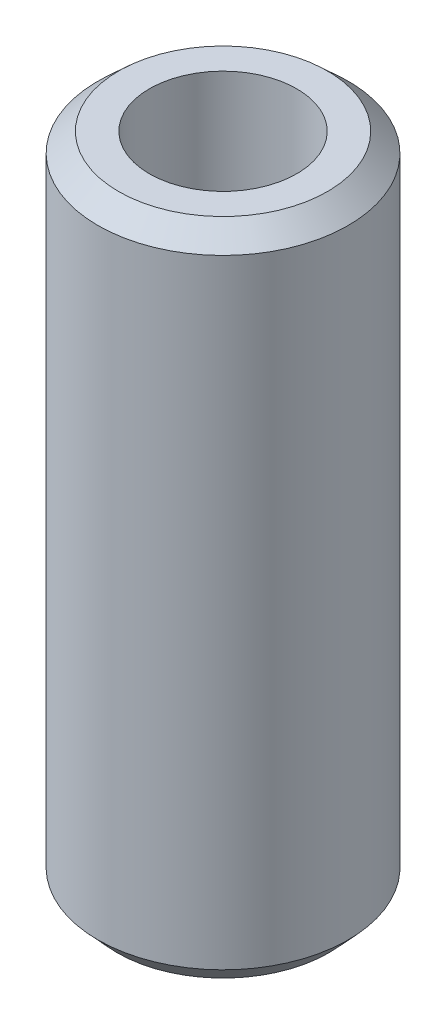
SolidWorks part; units mm, degrees
ref_plane "Front Plane" through (0, 0, 0) normal (0, 0, 1) x (1, 0, 0)
ref_plane "Top Plane" through (0, 0, 0) normal (0, 1, 0) x (1, 0, 0)
ref_plane "Right Plane" through (0, 0, 0) normal (1, 0, 0) x (0, 0, -1)
sketch "Sketch1" plane through (0, 0, 0) normal (0, 1, 0) x (1, 0, 0)
  circle A0 centre (0, 0) radius 10
  dimension "SHAFT_OD" = 20
extrude "Boss-Extrude1" add sketch "Sketch1" along normal blind 52.6283
sketch "Sketch2" plane through (0, 0, 0) normal (0, 1, 0) x (1, 0, 0)
  circle A0 centre (0, 0) radius 5.89
  dimension "BORE_D" = 11.78
extrude "Cut-Extrude1" cut sketch "Sketch2" along normal through all
chamfer "Chamfer1" distance 1.5254 angle 47.274 2 edges at (0, 52.6283, 10) (0, 0, 10) first distance on face at (0, 52.6283, 10) first distance on face at (0, 0, 5.89)
